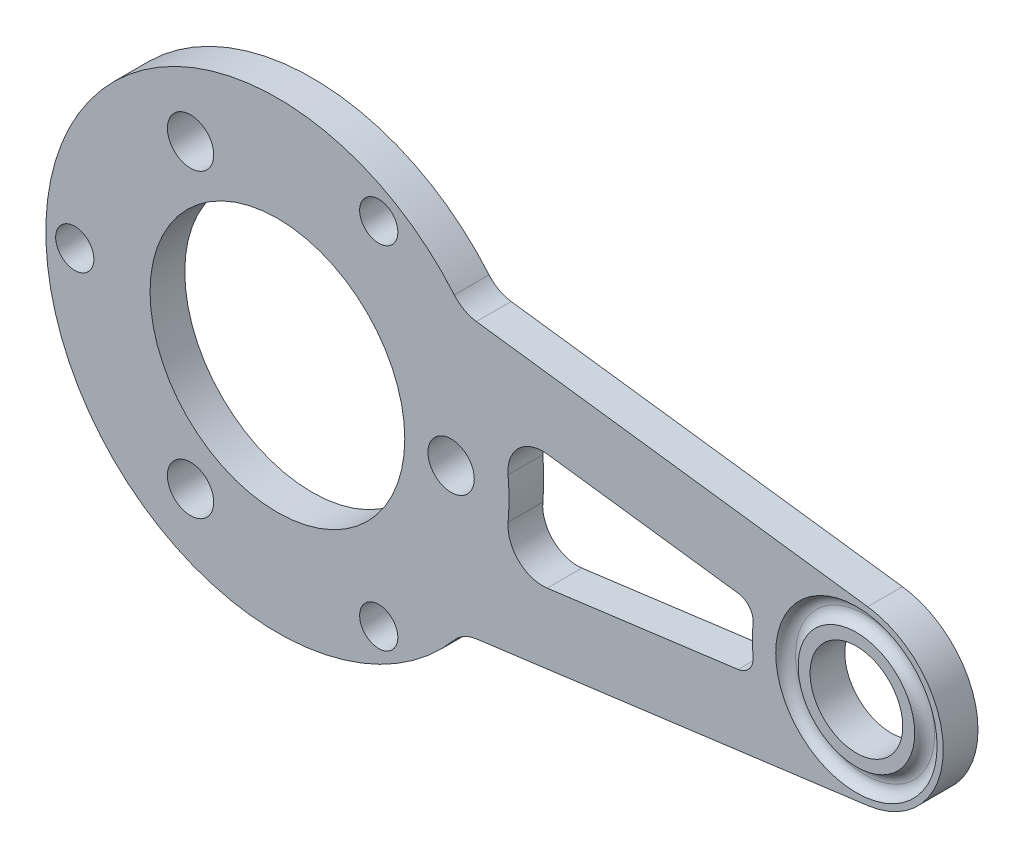
SolidWorks part; units mm, degrees
material "6061 合金"
ref_plane "前视基准面" through (0, 0, 0) normal (0, 0, 1) x (1, 0, 0)
ref_plane "上视基准面" through (0, 0, 0) normal (0, 1, 0) x (1, 0, 0)
ref_plane "右视基准面" through (0, 0, 0) normal (1, 0, 0) x (0, 0, -1)
other "Configuration Table"
sketch "草图1" plane through (0, 0, 0) normal (0, 0, 1) x (1, 0, 0)
  line L0 (0, 0) -> (50, 0) construction
  line L1 (1.82, -13.8812) -> (50.975, -7.4364)
  line L2 (1.82, 13.8812) -> (50.975, 7.4364)
  circle A0 centre (0, 0) radius 9 construction
  circle A1 centre (-9, 0) radius 1.65
  circle A2 centre (4.5, 7.7942) radius 1.65
  circle A3 centre (4.5, -7.7942) radius 1.65
  circle A4 centre (0, 0) radius 5
  circle A5 centre (50, 0) radius 4
  arc A6 (50.975, -7.4364) -> (50.975, 7.4364) centre (50, 0) ccw
  arc A7 (1.82, 13.8812) -> (1.82, -13.8812) centre (0, 0) ccw
  point P13 (0, 0)
  dimension "D2" = 18
  dimension "D3" = 3.3
  dimension "D5" = 10
  dimension "D6" = 8
  dimension "D7" = 15
  dimension "D8" = 28
  dimension "D1" = 50
  dimension "D4" = 3
extrude "凸台-拉伸1" add sketch "草图1" along normal blind 3
sketch "草图2" plane through (0, 0, 3) normal (0, 0, 1) x (1, 0, 0)
  line L4 (1.04, -7.9321) -> (50.195, -1.4873)
  line L5 (50.195, 1.4873) -> (1.04, 7.9321)
  line L6 (16.0771, -5.9606) -> (39.7841, -2.8523)
  line L7 (39.7841, 2.8523) -> (16.0771, 5.9606)
  arc A0 (14.4382, -4.0666) -> (14.4382, 4.0666) centre (0, 0) ccw
  arc A1 (41.0764, 1.17) -> (41.0764, -1.17) centre (50, 0) ccw
  arc A4 (41.0764, 1.17) -> (39.7841, 2.8523) centre (39.5891, 1.365) ccw
  arc A5 (14.4382, -4.0666) -> (16.0771, -5.9606) centre (15.8821, -4.4733) ccw
  arc A6 (1.04, 7.9321) -> (1.04, -7.9321) centre (0, 0) ccw
  arc A7 (50.195, -1.4873) -> (50.195, 1.4873) centre (50, 0) ccw
  arc A10 (14.4382, 4.0666) -> (16.0771, 5.9606) centre (15.8821, 4.4733) cw
  arc A11 (41.0764, -1.17) -> (39.7841, -2.8523) centre (39.5891, -1.365) cw
  dimension "D1" = 30
  dimension "D2" = 18
  dimension "D4" = 1.5
  dimension "D3" = 6
extrude "切除-拉伸1" cut sketch "草图2" against normal blind 5
sketch "草图3" plane through (0, 0, 3) normal (0, 0, 1) x (1, 0, 0)
  circle A0 centre (-9, 0) radius 2.55
  circle A1 centre (4.5, 7.7942) radius 2.55
  circle A2 centre (4.5, -7.7942) radius 2.55
  dimension "D1" = 5.1
extrude "切除-拉伸2" cut sketch "草图3" against normal blind 1 from offset 2 offset against normal yes
sketch "草图4" plane through (0, 0, 3) normal (0, 0, 1) x (1, 0, 0)
  circle A0 centre (0, 0) radius 20
  dimension "D1" = 40
extrude "凸台-拉伸2" add sketch "草图4" against normal through all
sketch "草图5" plane through (0, 0, 3) normal (0, 0, 1) x (1, 0, 0)
  line L0 (0, 0) -> (8.75, -15.1554) construction
  circle A0 centre (0, 0) radius 11
  circle A1 centre (0, 0) radius 17.5 construction
  circle A2 centre (-17.5, 0) radius 1.65
  circle A3 centre (8.75, 15.1554) radius 1.65
  circle A4 centre (8.75, -15.1554) radius 1.65
  circle A5 centre (0, 0) radius 15 construction
  circle A6 centre (-7.5, 12.9904) radius 2
  circle A7 centre (15, 0) radius 2
  circle A8 centre (-7.5, -12.9904) radius 2
  point P13 (0, 0)
  point P22 (0, 0)
  dimension "D1" = 22
  dimension "D2" = 35
  dimension "D3" = 3.3
  dimension "D5" = 30
  dimension "D6" = 4
  dimension "D4" = 3
  dimension "D7" = 3
extrude "切除-拉伸3" cut sketch "草图5" against normal through all
fillet "圆角1" radius 3 4 edges at (15.9817, -12.0244, 1.5) (19.2148, 5.5492, 1.5) (15.9817, 12.0244, 1.5) (19.2148, -5.5492, 1.5)
sketch "草图8" plane through (0, 0, 3) normal (0, 0, -1) x (-1, 0, 0)
  circle A0 centre (-50, 0) radius 7.5
extrude "凸台-拉伸4" add sketch "草图8" against normal blind 0.25
sketch "草图9" plane through (0, 0, 3.25) normal (0, 0, 1) x (1, 0, 0)
  circle A0 centre (50, 0) radius 7
  circle A1 centre (50, 0) radius 5
  dimension "D1" = 14
  dimension "D2" = 10
extrude "切除-拉伸4" cut sketch "草图9" against normal blind 1
fillet "圆角2" radius 1 2 edges at (55, 0, 2.25) (57, 0, 2.25)
sketch "草图11" plane through (0, 0, 3) normal (0, 0, -1) x (-1, 0, 0)
  circle A0 centre (-50, 0) radius 7.5
extrude "切除-拉伸6" cut sketch "草图11" against normal blind 0.25
